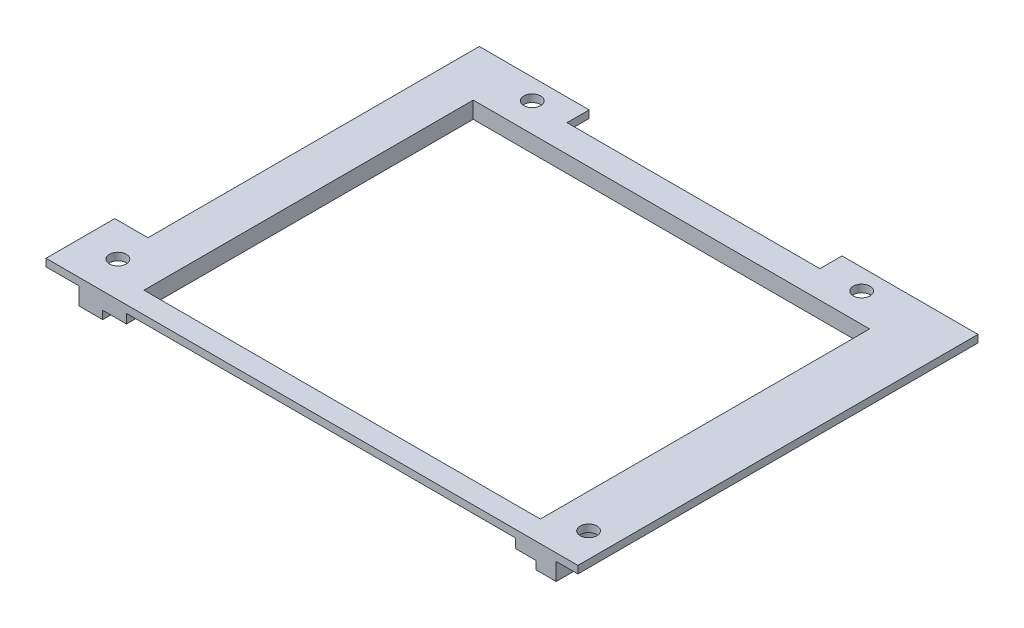
SolidWorks part; units mm, degrees
ref_plane "Front Plane" through (0, 0, 0) normal (0, 0, 1) x (1, 0, 0)
ref_plane "Top Plane" through (0, 0, 0) normal (0, 1, 0) x (1, 0, 0)
ref_plane "Right Plane" through (0, 0, 0) normal (1, 0, 0) x (0, 0, -1)
sketch "Sketch1" plane through (0, 0, 0) normal (0, 1, 0) x (1, 0, 0)
  line L0 (59.1034, 32.478) -> (59.1034, -39.482)
  line L1 (-22.7866, 23.578) -> (48.5034, 23.578)
  line L2 (-22.7866, 23.578) -> (-22.7866, -35.642)
  line L3 (-22.7866, -35.642) -> (48.5034, -35.642)
  line L4 (48.5034, 23.578) -> (48.5034, -35.642)
  line L5 (59.1034, -39.482) -> (-36.5666, -39.482)
  line L6 (-36.5666, -39.482) -> (-36.5666, -27.112)
  line L7 (-36.5666, -27.112) -> (-30.5966, -27.112)
  line L8 (-30.5966, -27.112) -> (-30.5966, 32.478)
  line L9 (-30.5966, 32.478) -> (-10.8366, 32.478)
  line L10 (-10.8366, 32.478) -> (-10.8366, 28.498)
  line L11 (-10.8366, 28.498) -> (34.6434, 28.498)
  line L12 (34.6434, 28.498) -> (34.6434, 32.478)
  line L13 (34.6434, 32.478) -> (59.1034, 32.478)
  line L15 (-30.5966, 28.498) -> (55.2034, 28.498)
  line L16 (-30.5966, 28.498) -> (-30.5966, -39.482)
  line L17 (-30.5966, -39.482) -> (55.2034, -39.482)
  line L18 (55.2034, 28.498) -> (55.2034, -39.482)
  line L19 (-22.0866, -35.642) -> (47.8834, -35.642)
  line L20 (-22.0866, -35.642) -> (-22.0866, -39.482)
  line L21 (-22.0866, -39.482) -> (47.8834, -39.482)
  line L22 (47.8834, -35.642) -> (47.8834, -39.482)
  line L23 (-26.3766, -39.482) -> (51.5534, -39.482)
  line L24 (-26.3766, -39.482) -> (-26.3766, 26.298)
  line L25 (-26.3766, 26.298) -> (51.5534, 26.298)
  line L26 (51.5534, -39.482) -> (51.5534, 26.298)
  circle A0 centre (-17.3716, 28.773) radius 1.515
  circle A1 centre (41.8884, 28.773) radius 1.515
  circle A2 centre (54.6884, -33.147) radius 1.515
  circle A3 centre (-29.9716, -33.147) radius 1.515
  circle A4 centre (-17.3716, 28.773) radius 2.9
  circle A5 centre (41.8884, 28.773) radius 2.9
  circle A6 centre (54.6884, -33.147) radius 2.9
  circle A7 centre (-29.9716, -33.147) radius 2.9
  dimension "D12" = 3.03
  dimension "D13" = 3.03
  dimension "D14" = 3.03
  dimension "D15" = 3.03
  dimension "D22" = 5.8
  dimension "D23" = 5.8
  dimension "D24" = 5.8
  dimension "D25" = 5.8
  dimension "D1" = 71.29
  dimension "D2" = 59.22
  dimension "D3" = 3.84
  dimension "D4" = 10.6
  dimension "D5" = 13.78
  dimension "D6" = 7.81
  dimension "D7" = 12.37
  dimension "D8" = 4.92
  dimension "D9" = 8.9
  dimension "D10" = 19.76
  dimension "D11" = 24.46
  dimension "D16" = 59.26
  dimension "D17" = 3.705
  dimension "D18" = 13.225
  dimension "D19" = 84.66
  dimension "D20" = 6.335
  dimension "D21" = 6.595
  dimension "D26" = 3.9
  dimension "D27" = 14.48
  dimension "D28" = 11.22
  dimension "D29" = 3.65
  dimension "D30" = 2.2
  dimension "D31" = 4.22
extrude "Boss-Extrude1" add sketch "Sketch1" against normal blind 1.34 contours A4 L15 L10 L9 L8 | L15 A4 A0 | A6 L18 L5 L0 L13 L12 L15 A5 | L15 A5 A1 | L18 A6 A2 | L22 L3 L20 L17 | A7 L16 L7 L6 L5 | L16 A7 A3 | L25 A4 L15 A0 | L25 A5 L15 A1 | L25 A5 | L25 A4 | L16 A7 A3 | L18 A6 A2 region at (58.3434, 0, 3.502) region at (51.8557, 0, 33.147) region at (56.3504, 0, 33.147) region at (-21.4922, 0, -30.6344) region at (41.7539, 0, -31.6037) region at (39.7, 0, -28.4363) region at (12.8984, 0, 37.562) region at (-14.965, 0, -27.2684) region at (-15.1832, 0, -28.5642) region at (41.8884, 0, -26.1269) region at (-17.3716, 0, -26.1269) region at (-33.8862, 0, 33.3194) region at (-31.6777, 0, 33.147) region at (-30.5287, 0, 35.2529)
extrude "Boss-Extrude2" add sketch "Sketch1<4>" against normal blind 3 contours A5 L25 A4 L24 L17 L20 L3 L2 L1 L4 L22 L26 region at (49.7184, 0, 38.4621)
sketch "Sketch1<4>" plane through (0, 0, 0) normal (0, 1, 0) x (1, 0, 0) same geometry as "Sketch1"
extrude "Boss-Extrude3" add sketch "Sketch1<6>" against normal blind 4.47 contours A7 L16 L5 L24 L25 A4 L15 L8 | A5 L15 L11 A4 L25 | A6 L18 L15 A5 L25 L26 L5 region at (53.0062, 0, 1.5798) region at (12.2584, 0, -27.3894) region at (-28.1779, 0, 2.1911)
sketch "Sketch1<6>" plane through (0, 0, 0) normal (0, 1, 0) x (1, 0, 0) same geometry as "Sketch1"
